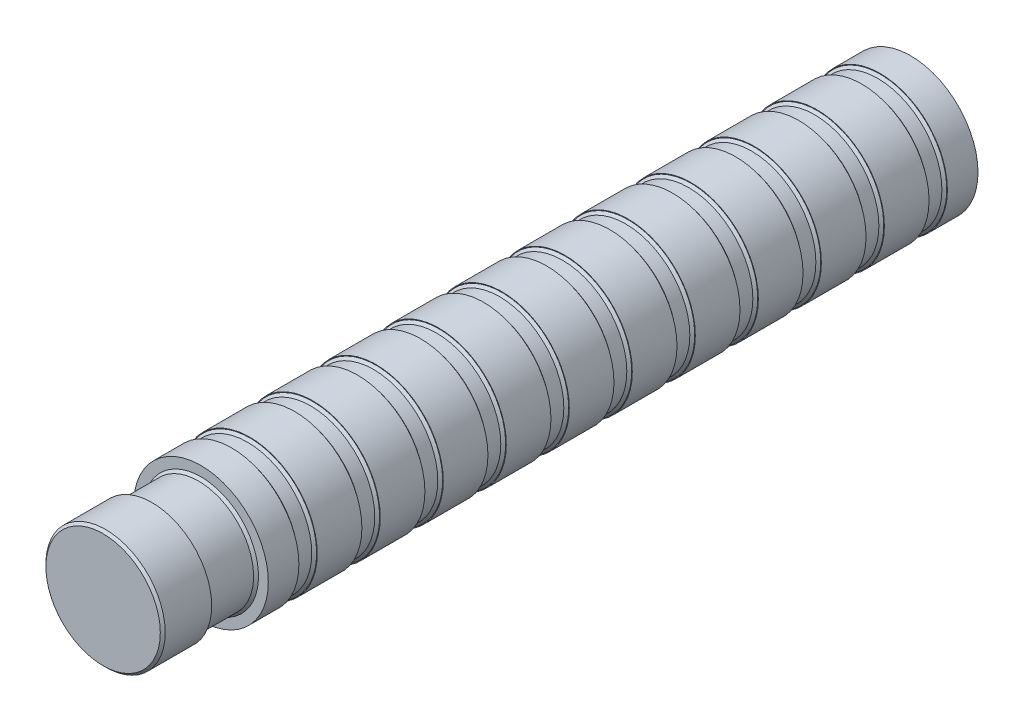
SolidWorks part; units mm, degrees
ref_plane "Front Plane" through (0, 0, 0) normal (0, 0, 1) x (1, 0, 0)
ref_plane "Top Plane" through (0, 0, 0) normal (0, 1, 0) x (1, 0, 0)
ref_plane "Right Plane" through (0, 0, 0) normal (1, 0, 0) x (0, 0, -1)
sketch "Sketch2" plane through (0, 0, 0) normal (1, 0, 0) x (0, 0, -1)
  line L0 (-29, 0) -> (29, 0)
  line L2 (-29, 5.5) -> (-26.5, 5.5)
  line L3 (29, 5.5) -> (29, 0)
  line L4 (-26.5, 5.5) -> (-26.5, 5.25)
  line L5 (-26.5, 5.25) -> (-25, 5.25)
  line L6 (-25, 5.25) -> (-25, 5.5)
  line L7 (-21.35, 5.5) -> (-21.35, 5.25)
  line L8 (-21.35, 5.25) -> (-19.85, 5.25)
  line L9 (-19.85, 5.25) -> (-19.85, 5.5)
  line L10 (-16.2, 5.5) -> (-16.2, 5.25)
  line L11 (-16.2, 5.25) -> (-14.7, 5.25)
  line L12 (-14.7, 5.25) -> (-14.7, 5.5)
  line L13 (-11.05, 5.5) -> (-11.05, 5.25)
  line L14 (-11.05, 5.25) -> (-9.55, 5.25)
  line L15 (-9.55, 5.25) -> (-9.55, 5.5)
  line L16 (-5.9, 5.5) -> (-5.9, 5.25)
  line L17 (-5.9, 5.25) -> (-4.4, 5.25)
  line L18 (-4.4, 5.25) -> (-4.4, 5.5)
  line L19 (-0.75, 5.5) -> (-0.75, 5.25)
  line L20 (-0.75, 5.25) -> (0.75, 5.25)
  line L21 (0.75, 5.25) -> (0.75, 5.5)
  line L22 (4.4, 5.5) -> (4.4, 5.25)
  line L23 (4.4, 5.25) -> (5.9, 5.25)
  line L24 (5.9, 5.25) -> (5.9, 5.5)
  line L25 (9.55, 5.5) -> (9.55, 5.25)
  line L26 (9.55, 5.25) -> (11.05, 5.25)
  line L27 (11.05, 5.25) -> (11.05, 5.5)
  line L28 (14.7, 5.5) -> (14.7, 5.25)
  line L29 (14.7, 5.25) -> (16.2, 5.25)
  line L30 (16.2, 5.25) -> (16.2, 5.5)
  line L31 (-25, 5.5) -> (-21.35, 5.5)
  line L32 (-19.85, 5.5) -> (-16.2, 5.5)
  line L33 (-14.7, 5.5) -> (-11.05, 5.5)
  line L34 (-9.55, 5.5) -> (-5.9, 5.5)
  line L35 (-4.4, 5.5) -> (-0.75, 5.5)
  line L36 (0.75, 5.5) -> (4.4, 5.5)
  line L37 (5.9, 5.5) -> (9.55, 5.5)
  line L38 (29, 0) -> (30.5762, 0) construction
  line L39 (11.05, 5.5) -> (14.7, 5.5)
  line L40 (16.2, 5.5) -> (19.85, 5.5)
  line L41 (19.85, 5.5) -> (19.85, 5.25)
  line L42 (19.85, 5.25) -> (21.35, 5.25)
  line L43 (21.35, 5.25) -> (21.35, 5.5)
  line L44 (25, 5.5) -> (25, 5.25)
  line L45 (25, 5.25) -> (26.5, 5.25)
  line L46 (26.5, 5.25) -> (26.5, 5.5)
  line L47 (21.35, 5.5) -> (25, 5.5)
  line L48 (26.5, 5.5) -> (29, 5.5)
  line L58 (-29, 5.5) -> (-29, 0)
  point P4 (0, 0)
  dimension "D1" = 58
  dimension "D2" = 2.5
  dimension "D3" = 1.5
  dimension "D4" = 0.25
  dimension "D7" = 2.5
  dimension "D8" = 3.65
  dimension "D13" = 5.5
  dimension "D6" = 11
revolve "Revolve2" add sketch "Sketch2" angle 360 about L38
sketch "Sketch3" plane through (0, 0, -29) normal (0, 0, -1) x (-1, 0, 0)
  line L0 (2.125, 0) -> (-2.125, 0) construction
  line L1 (1.475, 1.5297) -> (1.475, -1.5297)
  arc A0 (1.475, 1.5297) -> (1.475, -1.5297) centre (0, 0) ccw
  point P7 (0, 0)
  dimension "D1" = 4.25
  dimension "D2" = 3.6
extrude "Cut-Extrude1" cut sketch "Sketch3" against normal blind 14
sketch "Sketch5" plane through (0, 0, 29) normal (0, 0, 1) x (1, 0, 0)
  circle A0 centre (0, 0) radius 4.5
  dimension "D1" = 9
extrude "Boss-Extrude1" add sketch "Sketch5" along normal blind 4
sketch "Sketch6" plane through (0, 0, 33) normal (0, 0, 1) x (1, 0, 0)
  circle A0 centre (0, 0) radius 4.875
  dimension "D1" = 9.75
extrude "Boss-Extrude2" add sketch "Sketch6" along normal blind 4
chamfer "Chamfer1" distance 0.2 angle 45 25 edges at (4.875, 0, 37) (4.5, 0, 29) (4.5, 0, 33) (5.25, 0, 26.5) (5.25, 0, 25) (5.25, 0, 19.85) (5.25, 0, 21.35) (5.25, 0, -26.5) (5.25, 0, -25) (5.25, 0, -21.35) (5.25, 0, -19.85) (5.25, 0, -16.2) (5.25, 0, -14.7) (5.25, 0, -11.05) (5.25, 0, -9.55) (5.25, 0, -5.9) (5.25, 0, -4.4) (5.25, 0, -0.75) (5.25, 0, 0.75) (5.25, 0, 4.4) (5.25, 0, 5.9) (5.25, 0, 9.55) (5.25, 0, 11.05) (5.25, 0, 14.7) (5.25, 0, 16.2)
